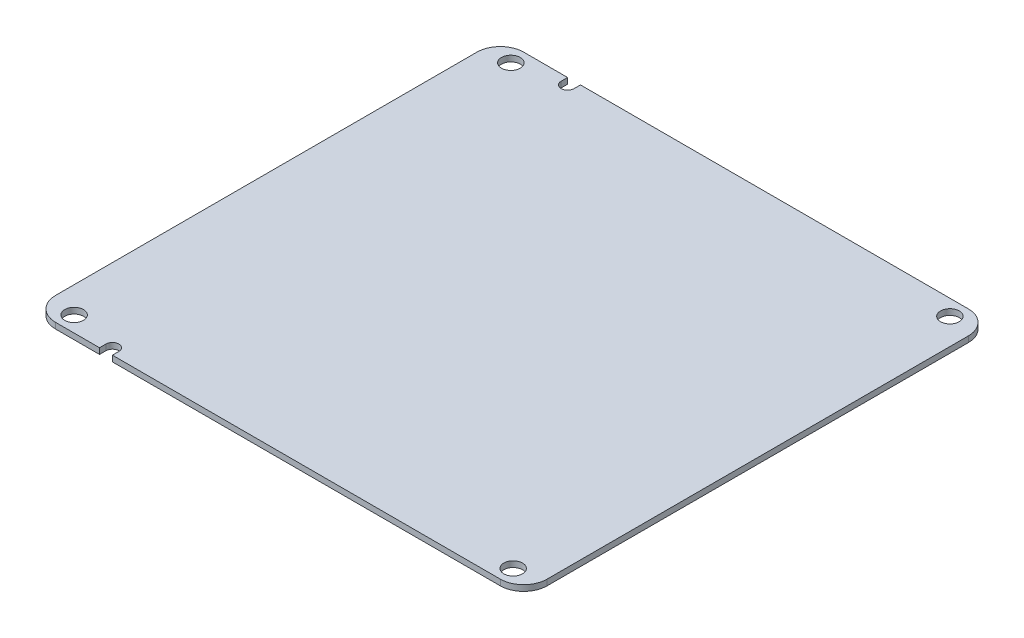
SolidWorks part; units mm, degrees
ref_plane "Front Plane" through (0, 0, 0) normal (0, 0, 1) x (1, 0, 0)
ref_plane "Top Plane" through (0, 0, 0) normal (0, 1, 0) x (1, 0, 0)
ref_plane "Right Plane" through (0, 0, 0) normal (1, 0, 0) x (0, 0, -1)
sketch "Sketch1" plane through (0, 0, 0) normal (0, 1, 0) x (1, 0, 0)
  line L1 (-52.5, 50) -> (52.5, 50)
  line L2 (-52.5, 50) -> (-52.5, -50)
  line L3 (-52.5, -50) -> (52.5, -50)
  line L4 (52.5, 50) -> (52.5, -50)
  line L5 (-52.5, 50) -> (52.5, -50) construction
  line L6 (-52.5, -50) -> (52.5, 50) construction
  point P0 (0, 0)
  dimension "D1" = 105
  dimension "D2" = 100
extrude "Main PCB" add sketch "Sketch1" along normal blind 1.25
fillet "Main PCB rounded corners" radius 5 4 edges at (-52.5, 0.625, -50) (52.5, 0.625, -50) (52.5, 0.625, 50) (-52.5, 0.625, 50)
sketch "Sketch2" plane through (0, 1.25, 0) normal (0, 1, 0) x (1, 0, 0)
  line L0 (-52.5, 0) -> (52.5, 0) construction
  line L1 (-52.5, 45) -> (-52.5, -45) construction
  line L2 (52.5, -45) -> (52.5, 45) construction
  line L3 (0, 50) -> (0, -50) construction
  line L4 (47.5, 50) -> (-47.5, 50) construction
  line L5 (-47.5, -50) -> (47.5, -50) construction
  line L6 (-38.125, -48.625) -> (-38.125, -50)
  line L7 (-35.375, -48.625) -> (-35.375, -50)
  line L8 (-35.375, 48.625) -> (-35.375, 50)
  line L9 (-38.125, 48.625) -> (-38.125, 50)
  circle A0 centre (-46.9, -46.65) radius 2
  circle A1 centre (46.9, -46.65) radius 2
  circle A2 centre (46.9, 46.65) radius 2
  circle A3 centre (-46.9, 46.65) radius 2
  circle A4 centre (-36.75, -48.625) radius 1.375
  circle A5 centre (-36.75, 48.625) radius 1.375
  line M3 (47.5, 50) -> (-47.5, 50)
  line M7 (-47.5, -50) -> (47.5, -50)
  dimension "D1" = 93.8
  dimension "D3" = 4
  dimension "D4" = 2.75
  dimension "D2" = 93.3
  dimension "D5" = 15.75
extrude "Main PCB holes" cut sketch "Sketch2" against normal up to next contours A3 | A2 | A1 | A0 | A4 | A4 L6 M7 | A4 L7 M7 | L9 A5 M3 | A5 | A5 L8 M3 region at (-37.8179, 1.25, 49.6929) region at (-36.75, 1.25, 48.625) region at (-35.6821, 1.25, 49.6929) region at (-35.6821, 1.25, -49.6929) region at (-36.75, 1.25, -48.625) region at (-37.8179, 1.25, -49.6929) region at (-46.9, 1.25, 46.65) region at (46.9, 1.25, 46.65) region at (46.9, 1.25, -46.65) region at (-46.9, 1.25, -46.65)
